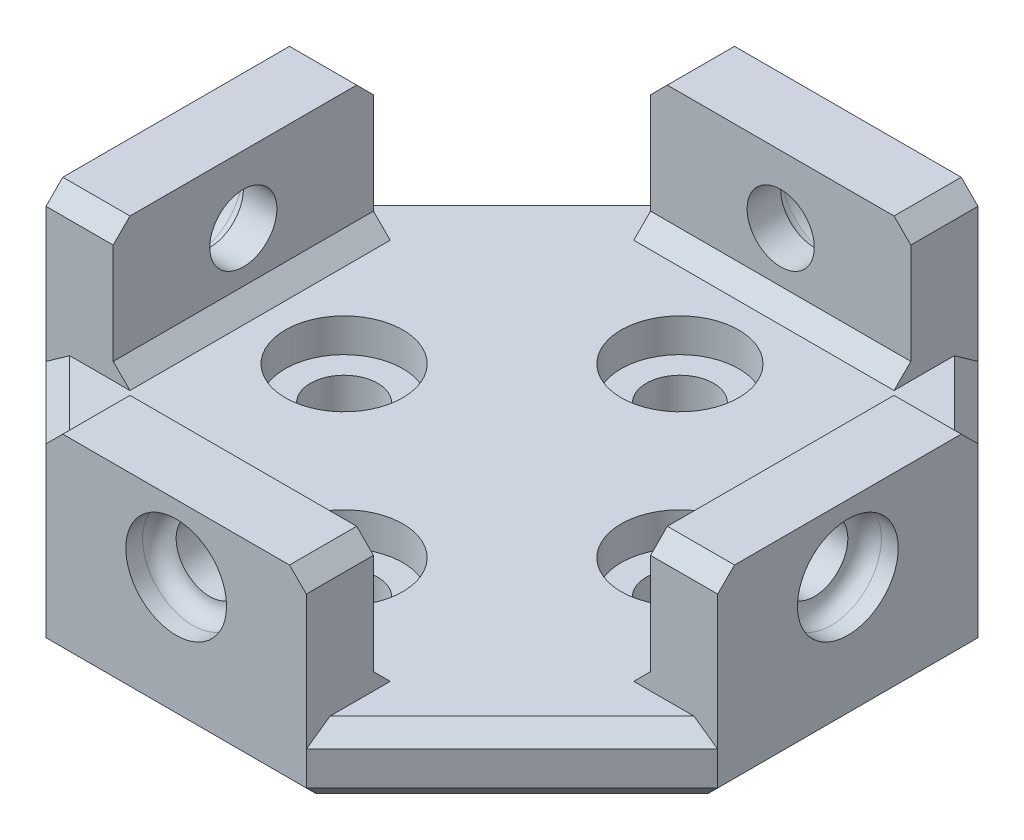
SolidWorks part; units mm, degrees
ref_plane "Front Plane" through (0, 0, 0) normal (0, 0, 1) x (1, 0, 0)
ref_plane "Top Plane" through (0, 0, 0) normal (0, 1, 0) x (1, 0, 0)
ref_plane "Right Plane" through (0, 0, 0) normal (1, 0, 0) x (0, 0, -1)
sketch "Sketch1" plane through (0, 0, 0) normal (0, 1, 0) x (1, 0, 0)
  line L1 (-20, 20) -> (20, 20)
  line L2 (-20, 20) -> (-20, -20)
  line L3 (-20, -20) -> (20, -20)
  line L4 (20, 20) -> (20, -20)
  line L5 (-20, 20) -> (20, -20) construction
  line L6 (-20, -20) -> (20, 20) construction
  point P0 (0, 0)
  dimension "D1" = 40
  dimension "D2" = 40
extrude "Boss-Extrude1" add sketch "Sketch1" along normal blind 4
sketch "Sketch2" plane through (0, 4, 0) normal (0, 1, 0) x (1, 0, 0)
  line L0 (0, 0) -> (-10, 0) construction
  circle A0 centre (-10, 0) radius 2
  circle A1 centre (0, 10) radius 2
  circle A2 centre (10, 0) radius 2
  circle A3 centre (0, -10) radius 2
  point P13 (0, 0)
  dimension "D2" = 4
  dimension "D1" = 10
  dimension "D3" = 4
extrude "Cut-Extrude1" cut sketch "Sketch2" against normal through all
sketch "Sketch3" plane through (0, 4, 0) normal (0, 1, 0) x (1, 0, 0)
  line L0 (0, 20) -> (0, -20) construction
  line L1 (20, 20) -> (-20, 20) construction
  line L2 (-20, -20) -> (20, -20) construction
  line L3 (-20, 0) -> (20, 0) construction
  line L4 (-20, 20) -> (-20, -20) construction
  line L5 (20, -20) -> (20, 20) construction
  line L7 (-7.75, 20) -> (-20, 20)
  line L9 (20, 7.75) -> (20, 20)
  line L10 (-20, 7.75) -> (-7.75, 20)
  line L11 (7.75, 20) -> (20, 7.75)
  line L12 (20, -7.75) -> (7.75, -20)
  line L13 (-20, -7.75) -> (-7.75, -20)
  line L14 (20, -20) -> (20, 20)
  line L15 (20, 20) -> (-20, 20)
  line L16 (-20, 20) -> (-20, -20)
  line L17 (-20, -20) -> (20, -20)
  line L18 (20, -20) -> (20, -7.75)
  line L19 (20, 20) -> (7.75, 20)
  line L20 (-20, 20) -> (-20, 7.75)
  line L21 (-20, -20) -> (-7.75, -20)
  line L22 (-20, -7.75) -> (-20, -20)
  line L23 (7.75, -20) -> (20, -20)
  point P24 (0, 0)
  point P25 (0, 0)
  dimension "D1" = 15.5
  dimension "D3" = 0
extrude "Cut-Extrude2" cut sketch "Sketch3" against normal through all
sketch "Sketch4" plane through (0, 4, 0) normal (0, 1, 0) x (1, 0, 0)
  line L0 (0, 20) -> (0, 16) construction
  line L1 (7.75, 20) -> (-7.75, 20) construction
  line L2 (16, 7.75) -> (20, -7.75) construction
  line L3 (-7.75, 16) -> (7.75, 16)
  line L4 (-7.75, 16) -> (-7.75, 20)
  line L5 (-7.75, 20) -> (7.75, 20)
  line L6 (7.75, 16) -> (7.75, 20)
  line L7 (-7.75, 16) -> (7.75, 20) construction
  line L8 (-7.75, 20) -> (7.75, 16) construction
  line L9 (20, 7.75) -> (16, -7.75) construction
  line L10 (16, 7.75) -> (20, 7.75)
  line L11 (16, 7.75) -> (16, -7.75)
  line L12 (16, -7.75) -> (20, -7.75)
  line L13 (20, 7.75) -> (20, -7.75)
  line L14 (7.75, -16) -> (-7.75, -20) construction
  line L15 (7.75, -20) -> (-7.75, -16) construction
  line L16 (7.75, -16) -> (7.75, -20)
  line L17 (7.75, -16) -> (-7.75, -16)
  line L18 (-7.75, -16) -> (-7.75, -20)
  line L19 (7.75, -20) -> (-7.75, -20)
  line L20 (-16, -7.75) -> (-20, 7.75) construction
  line L21 (-20, -7.75) -> (-16, 7.75) construction
  line L22 (-16, -7.75) -> (-20, -7.75)
  line L23 (-16, -7.75) -> (-16, 7.75)
  line L24 (-16, 7.75) -> (-20, 7.75)
  line L25 (-20, -7.75) -> (-20, 7.75)
  point P5 (0, 18)
  point P14 (18, 0)
  point P19 (0, -18)
  point P24 (-18, 0)
  point P29 (0, 0)
  dimension "D1" = 4
  dimension "D2" = 4
extrude "Boss-Extrude2" add sketch "Sketch4" along normal blind 8
sketch "Sketch5" plane through (16, 0, 0) normal (-1, 0, 0) x (0, 0, 1)
  line L0 (-7.75, 4) -> (7.75, 12) construction
  line L1 (-7.75, 12) -> (7.75, 4) construction
  circle A0 centre (0, 8) radius 2
  dimension "D1" = 4
extrude "Cut-Extrude3" cut sketch "Sketch5" against normal blind 5 and the other way through all
sketch "Sketch6" plane through (0, 0, 16) normal (0, 0, -1) x (-1, 0, 0)
  line L0 (-7.75, 12) -> (7.75, 4) construction
  line L3 (7.75, 12) -> (-7.75, 4) construction
  circle A0 centre (0, 8) radius 2
  dimension "D1" = 4
extrude "Cut-Extrude4" cut sketch "Sketch6" against normal blind 5 and the other way through all
sketch "Sketch7" plane through (0, 0, 20) normal (0, 0, 1) x (1, 0, 0)
  circle A0 centre (0, 8) radius 3
  dimension "D1" = 6
extrude "Cut-Extrude5" cut sketch "Sketch7" against normal blind 2
sketch "Sketch9" plane through (0, 0, 0) normal (1, 0, 0) x (0, 0, -1)
  line L0 (0, -4.8173) -> (0, 19.0183) construction
pattern_circular "CirPattern1" count 4 every 90 about axis through (0, -4.8173, 0) along (0, 1, 0) of "Cut-Extrude5"
chamfer "Chamfer1" distance 1 angle 45 16 edges at (13.875, 0, 13.875) (20, 0, 0) (13.875, 0, -13.875) (0, 0, -20) (-13.875, 0, -13.875) (-20, 0, 0) (-13.875, 0, 13.875) (0, 0, 20) (-18, 12, 7.75) (-18, 12, -7.75) (-7.75, 12, -18) (7.75, 12, -18) (18, 12, -7.75) (18, 12, 7.75) (7.75, 12, 18) (-7.75, 12, 18)
fillet "Fillet1" radius 1 4 edges at (18, 8, -3) (-3, 8, -18) (-18, 8, 3) (3, 8, 18)
chamfer "Chamfer2" distance 1 angle 45 8 edges at (-13.875, 4, -13.875) (13.875, 4, -13.875) (13.875, 4, 13.875) (-13.875, 4, 13.875) (16, 4, 0) (0, 4, -16) (-16, 4, 0) (0, 4, 16)
sketch "Sketch10" plane through (0, 4, 0) normal (0, 1, 0) x (1, 0, 0)
  circle A0 centre (-10, 0) radius 3.5
  circle A1 centre (0, 10) radius 3.5
  circle A2 centre (10, 0) radius 3.5
  circle A3 centre (0, -10) radius 3.5
  dimension "D1" = 7
extrude "Cut-Extrude6" cut sketch "Sketch10" against normal blind 2
